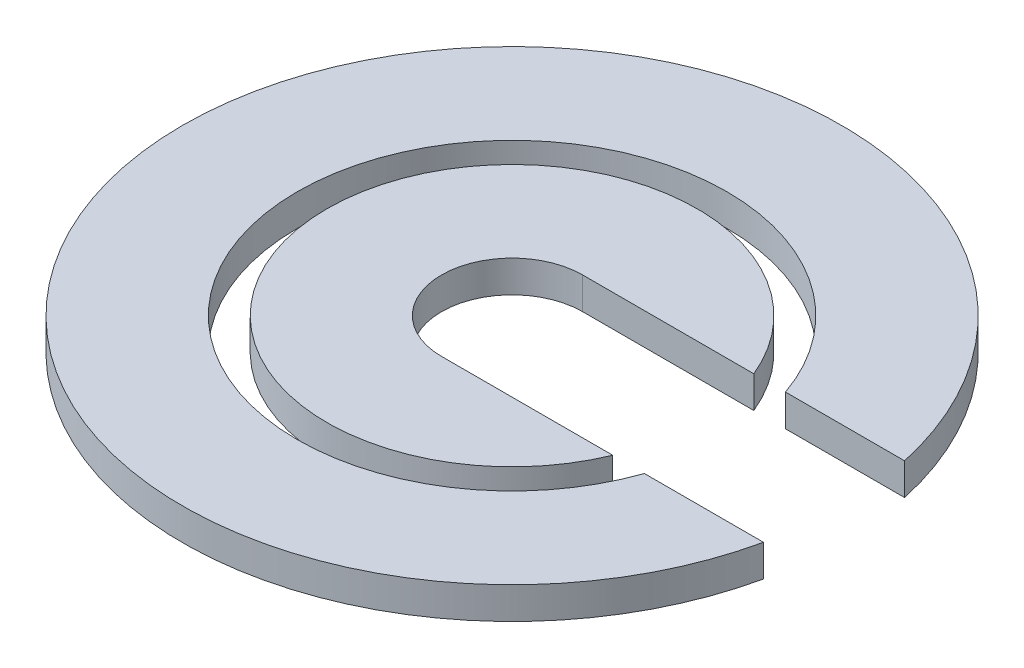
SolidWorks part; units mm, degrees
material "Bismuth"
ref_plane "Front" through (0, 0, 0) normal (0, 0, 1) x (1, 0, 0)
ref_plane "Top" through (0, 0, 0) normal (0, 1, 0) x (1, 0, 0)
ref_plane "Right" through (0, 0, 0) normal (1, 0, 0) x (0, 0, -1)
sketch "Sketch1" plane through (0, 0, 0) normal (0, 1, 0) x (1, 0, 0)
  line L0 (0, 28.575) -> (69.3431, 28.575)
  line L1 (0, -28.575) -> (69.3431, -28.575)
  line L2 (82.1734, -28.575) -> (130.4067, -28.575)
  line L3 (82.1734, 28.575) -> (130.4067, 28.575)
  arc A0 (82.1734, 28.575) -> (82.1734, -28.575) centre (0, 0) ccw
  arc A1 (130.4067, 28.575) -> (130.4067, -28.575) centre (0, 0) ccw
  arc A2 (69.3431, 28.575) -> (69.3431, -28.575) centre (0, 0) ccw
  arc A3 (0, 28.575) -> (0, -28.575) centre (0, 0) ccw
extrude "Boss-Extrude1" add sketch "Sketch1" along normal blind 12.9 contours A3 L1 A2 L0
extrude "Boss-Extrude2" add sketch "Sketch1<21>" along normal blind 12.9 separate body contours A0 L2 A1 L3
sketch "Sketch1<21>" plane through (0, 0, 0) normal (0, 1, 0) x (1, 0, 0) same geometry as "Sketch1"
